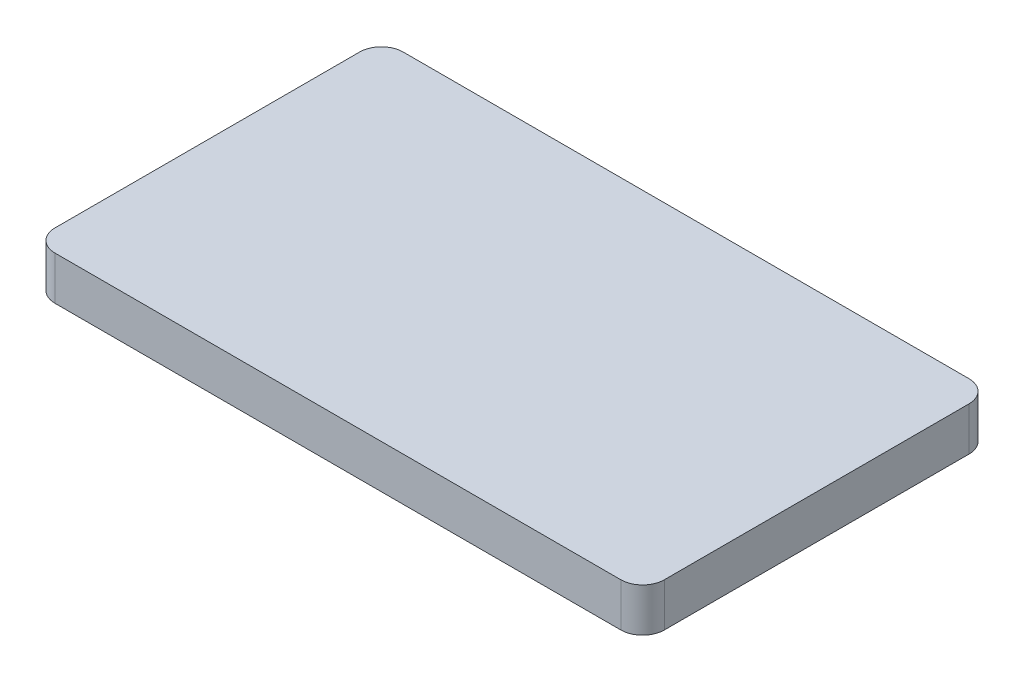
SolidWorks part; units mm, degrees
ref_plane "Спереди" through (0, 0, 0) normal (0, 0, 1) x (1, 0, 0)
ref_plane "Сверху" through (0, 0, 0) normal (0, 1, 0) x (1, 0, 0)
ref_plane "Справа" through (0, 0, 0) normal (1, 0, 0) x (0, 0, -1)
sketch "Эскиз1" plane through (0, 0, 0) normal (0, 1, 0) x (1, 0, 0)
  line L1 (3.5, -2) -> (-3.5, -2)
  line L2 (3.5, -2) -> (3.5, 2)
  line L3 (3.5, 2) -> (-3.5, 2)
  line L4 (-3.5, -2) -> (-3.5, 2)
  line L5 (3.5, -2) -> (-3.5, 2) construction
  line L6 (3.5, 2) -> (-3.5, -2) construction
  point P0 (0, 0)
  dimension "D1" = 7
  dimension "D2" = 4
extrude "Бобышка-Вытянуть1" add sketch "Эскиз1" along normal blind 0.5
fillet "Скругление1" radius 0.25 4 edges at (-3.5, 0.25, -2) (3.5, 0.25, -2) (3.5, 0.25, 2) (-3.5, 0.25, 2)
